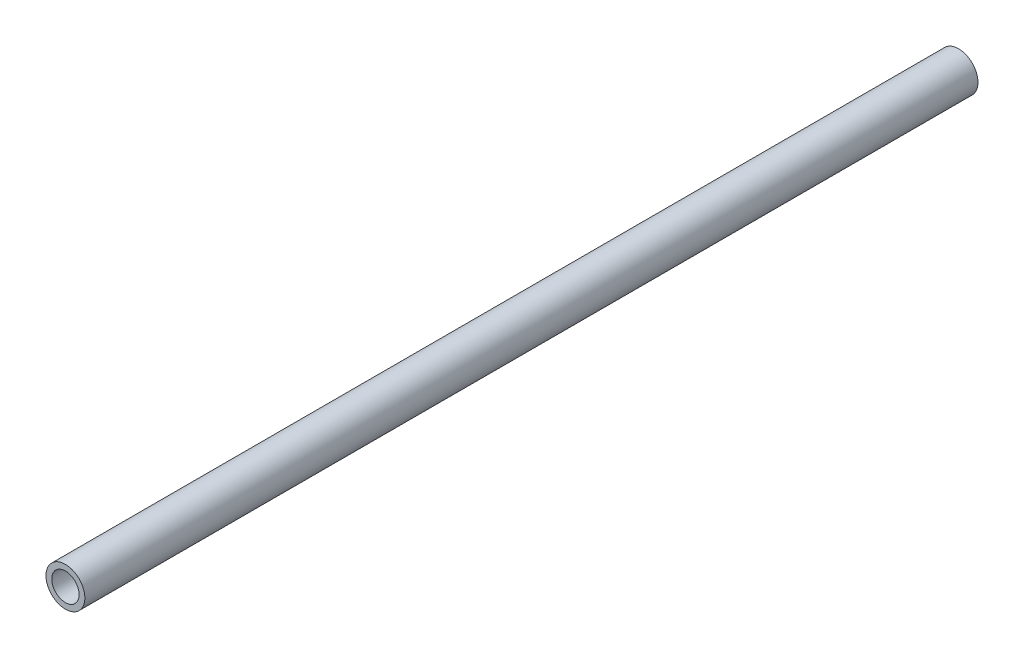
SolidWorks part; units mm, degrees
material "Galvanized Steel"
ref_plane "Front Plane" through (0, 0, 0) normal (0, 0, 1) x (1, 0, 0)
ref_plane "Top Plane" through (0, 0, 0) normal (0, 1, 0) x (1, 0, 0)
ref_plane "Right Plane" through (0, 0, 0) normal (1, 0, 0) x (0, 0, -1)
sketch "Sketch1" plane through (0, 0, 0) normal (0, 0, 1) x (1, 0, 0)
  circle A0 centre (347.5, -20) radius 13.5
  circle A1 centre (347.5, -20) radius 9.5
  dimension "D1" = 27
  dimension "D2" = 19
extrude "Boss-Extrude1" add sketch "Sketch1" along normal blind 620
ref_point "Point1"
ref_axis "Axis1" through (347.5, -20, 620) along (0, 0, -1)
ref_axis "Axis2" through (347.5, -20, 0) along (0, 0, -1)
ref_plane "Plane1" through (347.5, 0, 0) normal (1, 0, 0) x (0, 0, -1)
